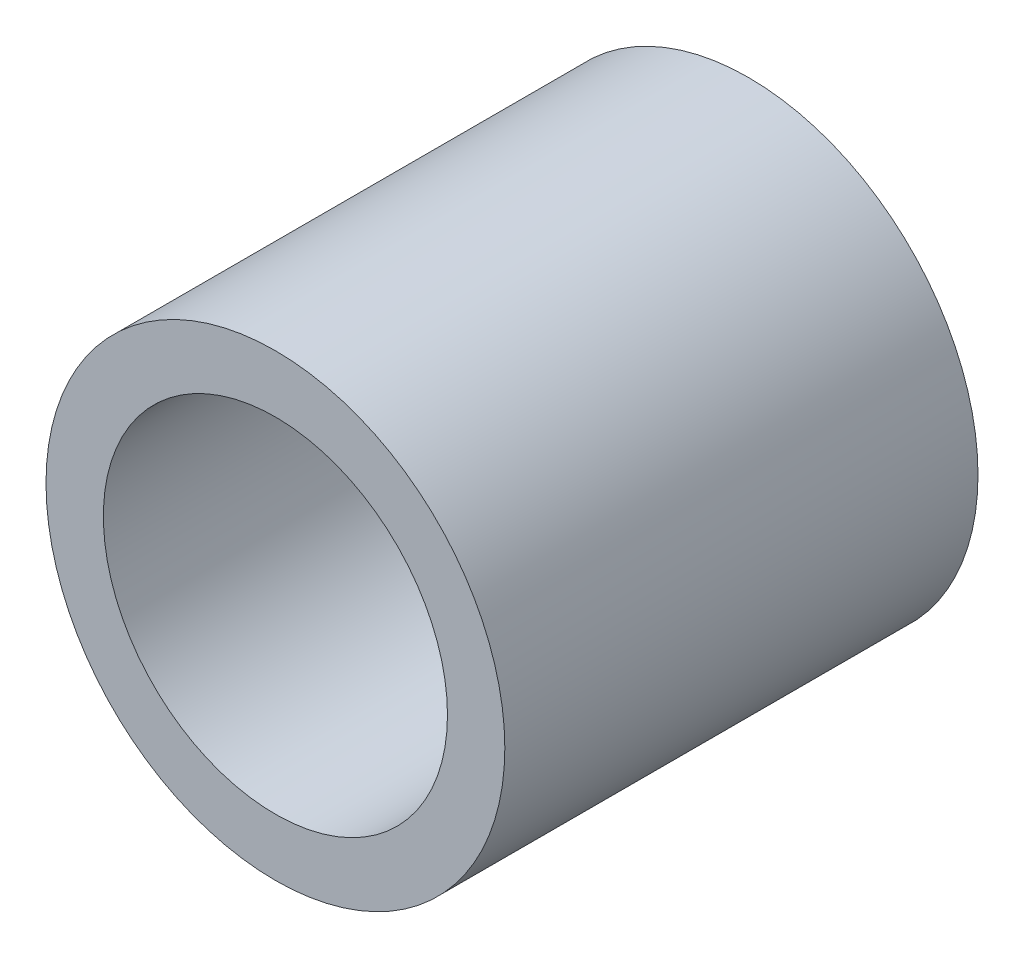
SolidWorks part; units mm, degrees
ref_plane "Płaszczyzna przednia" through (0, 0, 0) normal (0, 0, 1) x (1, 0, 0)
ref_plane "Płaszczyzna górna" through (0, 0, 0) normal (0, 1, 0) x (1, 0, 0)
ref_plane "Płaszczyzna prawa" through (0, 0, 0) normal (1, 0, 0) x (0, 0, -1)
sketch "Sketch1" plane through (0, 0, 0) normal (0, 0, 1) x (1, 0, 0)
  circle A0 centre (0, 0) radius 6
  circle A1 centre (0, 0) radius 8
  dimension "D1" = 12
  dimension "D2" = 2
extrude "Boss-Extrude1" add sketch "Sketch1" along normal blind 16.5
